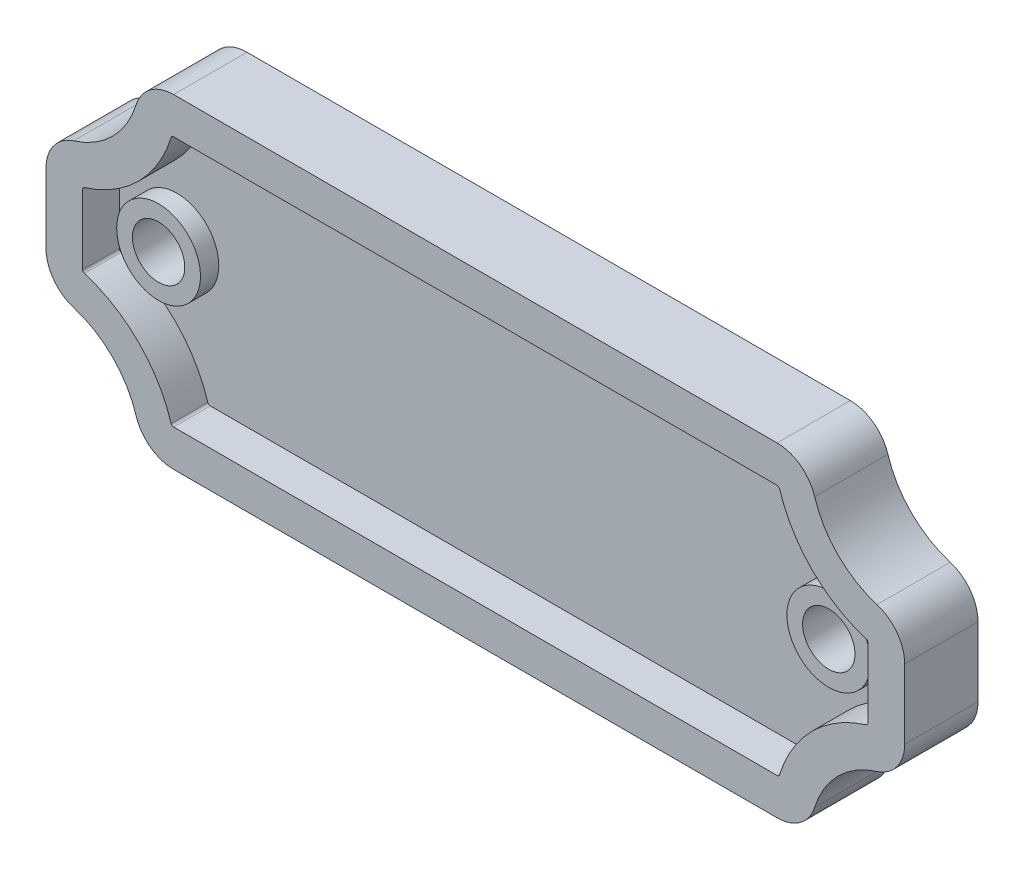
SolidWorks part; units mm, degrees
material "Brass"
ref_plane "Front Plane" through (0, 0, 0) normal (0, 0, 1) x (1, 0, 0)
ref_plane "Top Plane" through (0, 0, 0) normal (0, 1, 0) x (1, 0, 0)
ref_plane "Right Plane" through (0, 0, 0) normal (1, 0, 0) x (0, 0, -1)
sketch "Sketch8" plane through (0, 0, 0) normal (0, 0, 1) x (1, 0, 0)
  line L0 (0, -3.3139) -> (0, 3.3139)
  line L1 (12.1861, 15.5) -> (69.8139, 15.5)
  line L2 (0, 0) -> (41, 0)
  line L3 (12.1861, -15.5) -> (69.8139, -15.5)
  line L4 (41, 15.5) -> (41, -15.5)
  line L5 (82, -3.3139) -> (82, 3.3139)
  line L6 (12.1861, -12) -> (69.8139, -12)
  line L7 (3.5, -3.3139) -> (3.5, 3.3139)
  line L8 (12.1861, 12) -> (69.8139, 12)
  line L9 (78.5, -3.3139) -> (78.5, 3.3139)
  line L10 (3.5, -3.3139) -> (3.5, 3.3139)
  line L11 (69.8139, 12) -> (12.1861, 12)
  line L12 (78.5, -3.3139) -> (78.5, 3.3139)
  line L13 (69.8139, -12) -> (12.1861, -12)
  arc A0 (2.6471, 6.8981) -> (8.6019, 12.8529) centre (0, 15.5) ccw
  arc A1 (8.6019, 12.8529) -> (12.1861, 15.5) centre (12.1861, 11.75) cw
  arc A2 (0, 3.3139) -> (2.6471, 6.8981) centre (3.75, 3.3139) cw
  arc A3 (0, -3.3139) -> (2.6471, -6.8981) centre (3.75, -3.3139) ccw
  arc A4 (8.6019, -12.8529) -> (12.1861, -15.5) centre (12.1861, -11.75) ccw
  arc A5 (2.6471, -6.8981) -> (8.6019, -12.8529) centre (0, -15.5) cw
  arc A6 (79.3529, -6.8981) -> (73.3981, -12.8529) centre (82, -15.5) ccw
  arc A7 (73.3981, -12.8529) -> (69.8139, -15.5) centre (69.8139, -11.75) cw
  arc A8 (82, -3.3139) -> (79.3529, -6.8981) centre (78.25, -3.3139) cw
  arc A9 (82, 3.3139) -> (79.3529, 6.8981) centre (78.25, 3.3139) ccw
  arc A10 (73.3981, 12.8529) -> (69.8139, 15.5) centre (69.8139, 11.75) ccw
  arc A11 (79.3529, 6.8981) -> (73.3981, 12.8529) centre (82, 15.5) cw
  arc A12 (78.3235, -3.5529) -> (70.0529, -11.8235) centre (82, -15.5) ccw
  arc A13 (70.0529, -11.8235) -> (69.8139, -12) centre (69.8139, -11.75) cw
  arc A14 (11.9471, -11.8235) -> (12.1861, -12) centre (12.1861, -11.75) ccw
  arc A15 (3.6765, -3.5529) -> (11.9471, -11.8235) centre (0, -15.5) cw
  arc A16 (3.5, -3.3139) -> (3.6765, -3.5529) centre (3.75, -3.3139) ccw
  arc A17 (3.5, 3.3139) -> (3.6765, 3.5529) centre (3.75, 3.3139) cw
  arc A18 (3.6765, 3.5529) -> (11.9471, 11.8235) centre (0, 15.5) ccw
  arc A19 (11.9471, 11.8235) -> (12.1861, 12) centre (12.1861, 11.75) cw
  arc A20 (70.0529, 11.8235) -> (69.8139, 12) centre (69.8139, 11.75) ccw
  arc A21 (78.3235, 3.5529) -> (70.0529, 11.8235) centre (82, 15.5) cw
  arc A22 (78.5, 3.3139) -> (78.3235, 3.5529) centre (78.25, 3.3139) ccw
  arc A23 (78.5, -3.3139) -> (78.3235, -3.5529) centre (78.25, -3.3139) cw
  circle A24 centre (9, 0) radius 2.5
  circle A25 centre (73, 0) radius 2.5
  circle A26 centre (9, 0) radius 4
  circle A27 centre (73, 0) radius 2.5
  circle A28 centre (73, 0) radius 4
  arc A29 (3.5, -3.3139) -> (3.6765, -3.5529) centre (3.75, -3.3139) ccw
  arc A30 (3.5, 3.3139) -> (3.6765, 3.5529) centre (3.75, 3.3139) cw
  arc A31 (3.6765, 3.5529) -> (11.9471, 11.8235) centre (0, 15.5) ccw
  arc A32 (11.9471, 11.8235) -> (12.1861, 12) centre (12.1861, 11.75) cw
  arc A33 (70.0529, 11.8235) -> (69.8139, 12) centre (69.8139, 11.75) ccw
  arc A34 (78.3235, 3.5529) -> (70.0529, 11.8235) centre (82, 15.5) cw
  arc A35 (78.5, 3.3139) -> (78.3235, 3.5529) centre (78.25, 3.3139) ccw
  arc A36 (78.5, -3.3139) -> (78.3235, -3.5529) centre (78.25, -3.3139) cw
  arc A37 (78.3235, -3.5529) -> (70.0529, -11.8235) centre (82, -15.5) ccw
  arc A38 (70.0529, -11.8235) -> (69.8139, -12) centre (69.8139, -11.75) cw
  arc A39 (11.9471, -11.8235) -> (12.1861, -12) centre (12.1861, -11.75) ccw
  arc A40 (3.6765, -3.5529) -> (11.9471, -11.8235) centre (0, -15.5) cw
  point P67 (0, 0)
  dimension "D1" = 3.75
  dimension "D2" = 9
  dimension "D6" = 5
  dimension "D8" = 8
  dimension "D3" = 31
  dimension "D4" = 82
  dimension "D7" = 9
  dimension "D5" = 3.5
extrude "Boss-Extrude3" add sketch "Sketch8" against normal blind 1.75 and the other way blind 5.25 contours L2 A26 A24 | L2 A26 A24 | A28 A25 region at (9, 3.9106, 0) region at (5.75, -0.0894, 0) region at (69.1131, 0, 0)
extrude "Boss-Extrude4" add sketch "Sketch8<4>" along normal blind 3.5 separate body contours A26 L2 L4 L8 A19 A18 A17 L7 | A26 L2 L7 A16 A15 A14 L6 L4 | A23 L9 A22 A21 A20 L8 L4 L6 A13 A12 A28 region at (25.1311, 5.9397, 0) region at (25.1311, -5.9397, 0) region at (56.8689, 0, 0)
sketch "Sketch8<4>" plane through (0, 0, 0) normal (0, 0, 1) x (1, 0, 0) same geometry as "Sketch8"
extrude "Boss-Extrude5" add sketch "Sketch8<6>" along normal blind 7 separate body contours A18 A19 L8 L4 L1 A1 A0 A2 L0 L2 L7 A17 | L9 A23 A12 A13 L6 L4 L3 A7 A6 A8 L5 A9 A11 A10 L1 L8 A20 A21 A22 | A16 L7 L2 L0 A3 A5 A4 L3 L4 L6 A14 A15 region at (0.4383, -1.657, 0) region at (0.4383, 1.657, 0) region at (41.514, -13.75, 0)
sketch "Sketch8<6>" plane through (0, 0, 0) normal (0, 0, 1) x (1, 0, 0) same geometry as "Sketch8"
equation "\"A\" = 3.5mm"
equation "\"B\" = 82mm"
equation "\"D4@Sketch8\"=\"B\""
equation "\"D1@Boss-Extrude3\"=\"A\"*0.5mm"
equation "\"D1@Boss-Extrude4\"=\"A\""
equation "\"D5@Sketch8\"=\"A\""
equation "\"D2@Boss-Extrude3\"=\"A\"*1.5mm"
equation "\"D1@Boss-Extrude5\"=\"A\"*2mm"
